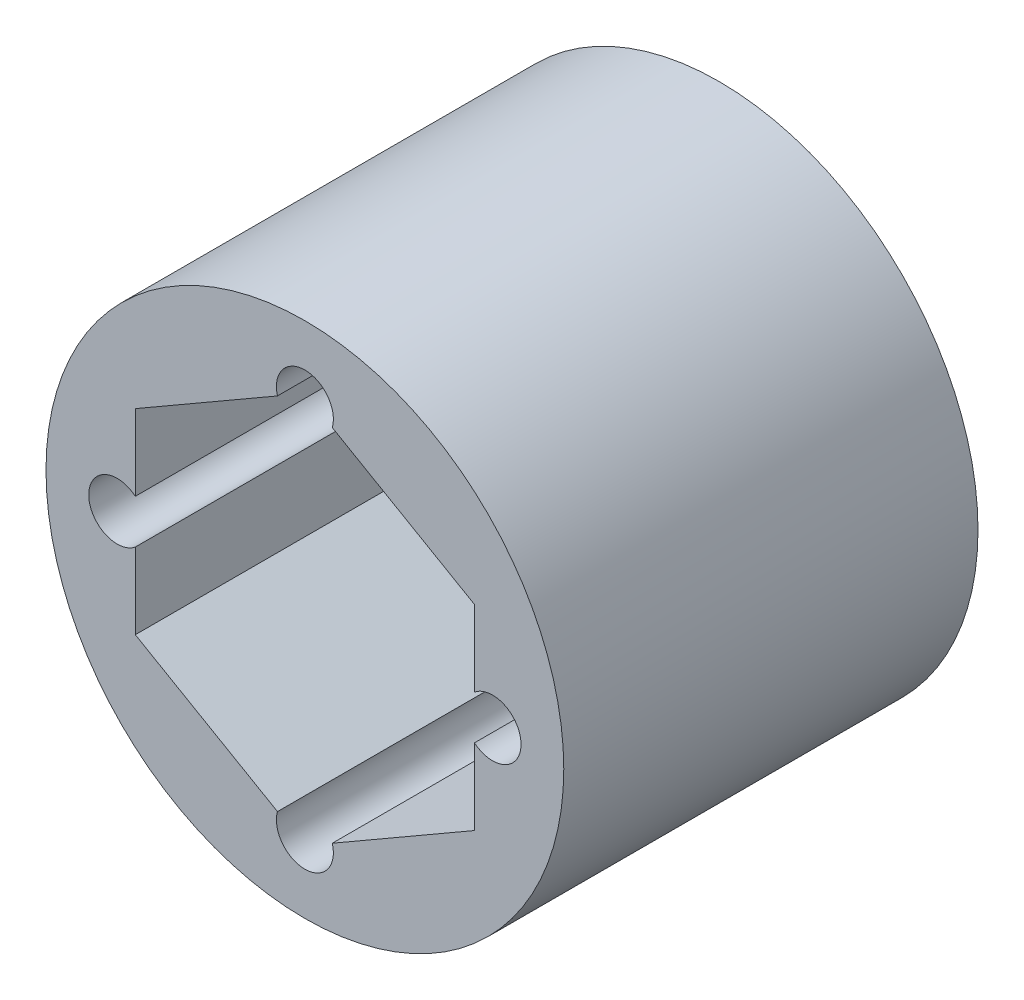
SolidWorks part; units mm, degrees
ref_plane "Front Plane" through (0, 0, 0) normal (0, 0, 1) x (1, 0, 0)
ref_plane "Top Plane" through (0, 0, 0) normal (0, 1, 0) x (1, 0, 0)
ref_plane "Right Plane" through (0, 0, 0) normal (1, 0, 0) x (0, 0, -1)
sketch "Sketch1" plane through (0, 0, 0) normal (0, 0, 1) x (1, 0, 0)
  line L0 (0, 0) -> (0, 12.391) construction
  circle A0 centre (0, 0) radius 10
  circle A1 centre (0, 7.25) radius 1.1
  circle A2 centre (0, 0) radius 4.25
  circle A3 centre (7.25, 0) radius 1.1
  circle A4 centre (0, -7.25) radius 1.1
  circle A5 centre (-7.25, 0) radius 1.1
  dimension "D1" = 20
  dimension "D2" = 2.2
  dimension "D4" = 8.5
  dimension "D3" = 7.25
  dimension "D5" = 4
extrude "Boss-Extrude1" add sketch "Sketch1" along normal blind 16
sketch "Sketch2" plane through (0, 0, 16) normal (0, 0, 1) x (1, 0, 0)
  line L1 (0, 7.5633) -> (-6.55, 3.7816)
  line L2 (-6.55, 3.7816) -> (-6.55, -3.7816)
  line L3 (-6.55, -3.7816) -> (0, -7.5633)
  line L4 (0, -7.5633) -> (6.55, -3.7816)
  line L5 (6.55, -3.7816) -> (6.55, 3.7816)
  line L6 (6.55, 3.7816) -> (0, 7.5633)
  circle A0 centre (0, 0) radius 6.55 construction
  dimension "D1" = 13.1
extrude "Cut-Extrude1" cut sketch "Sketch2" against normal blind 14
